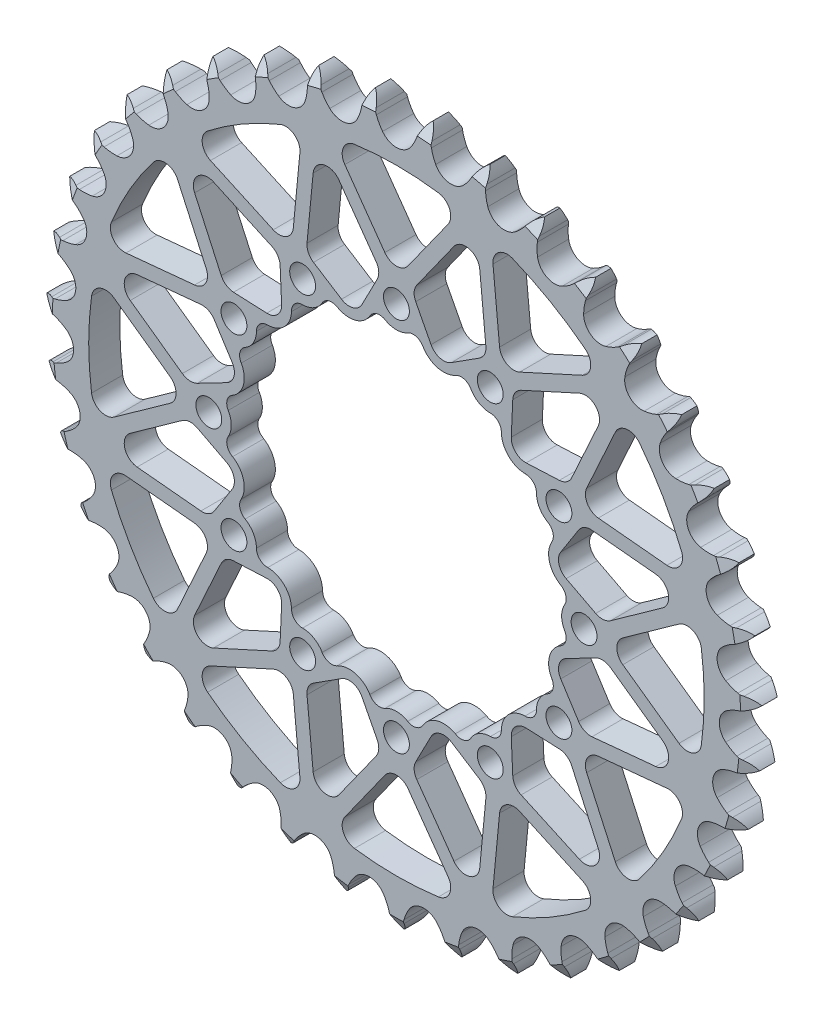
SolidWorks part; units mm, degrees
material "7075-T6 (SN)"
ref_plane "Front Plane" through (0, 0, 0) normal (0, 0, 1) x (1, 0, 0)
ref_plane "Top Plane" through (0, 0, 0) normal (0, 1, 0) x (1, 0, 0)
ref_plane "Right Plane" through (0, 0, 0) normal (1, 0, 0) x (0, 0, -1)
sketch "Work Sketch" plane through (0, 0, 0) normal (0, 0, 1) x (1, 0, 0)
  line L0 (0, 0) -> (0, 160.4542) construction
  line L1 (-112.0919, 78.9148) -> (87.2579, 78.9148) construction
  line L2 (5.102, 120.8822) -> (5.102, 112.9699) construction
  line L3 (-12.8497, 82.6953) -> (16.7256, 82.6953) construction
  line L4 (5.102, 82.6953) -> (-6.0879, 74.4036) construction
  line L5 (5.102, 82.6953) -> (-4.6505, 79.1506) construction
  line L6 (-4.6505, 79.1506) -> (-6.8863, 85.3019)
  line L7 (-11.5114, 78.0206) -> (-7.1525, 78.0206) construction
  line L8 (-11.0765, 124.7602) -> (-11.0765, 110.2345) construction
  line L9 (0, 0) -> (-3.4402, 42.6146) construction
  circle A0 centre (0, 0) radius 78.9148
  circle A1 centre (0, 78.9148) radius 4.0088
  arc A2 (-4.6505, 79.1506) -> (-3.2209, 76.5281) centre (5.0804, 82.7541) ccw
  circle A3 centre (-11.0765, 78.0206) radius 6.4254
  point P23 (-3.2209, 76.5281)
  dimension "D1" = 157.8295
  dimension "D8" = 10.3767
  dimension "D2" = 8.0177
  dimension "D3" = 5.102
  dimension "D4" = 3.7806
  dimension "D5" = 36.538
  dimension "D6" = 16.564
  dimension "D7" = 10.3767
  dimension "D9" = 0.8942
  dimension "D10" = 11.0765
  dimension "D11" = 4.615
sketch "Teeth Sketch" plane through (0, 0, 0) normal (0, 0, 1) x (1, 0, 0)
  line L0 (5.0376, 80.2155) -> (4.6505, 79.1506)
  line L1 (-7.4865, 92.7372) -> (-4.7839, 59.2593) construction
  line L2 (0, 0) -> (-10.9133, 132.3061) construction
  line L3 (7.8951, 79.9848) -> (8.1063, 78.8717)
  line L4 (16093.3137, -199351.4616) -> (-16096.7539, 199394.0762) construction
  line L5 (0, 146.3285) -> (0, 56.9858) construction
  line L6 (17.8398, 78.3686) -> (17.287, 77.3797)
  line L7 (0, -200000) -> (0, 200160.4542) construction
  line L8 (20.6234, 77.6826) -> (20.6533, 76.5499)
  line L9 (-4.6505, 79.1506) -> (-6.8863, 85.3019) construction
  line L10 (44.1616, 67.154) -> (43.8313, 66.0702)
  line L11 (-5.0376, 80.2155) -> (-4.6505, 79.1506)
  line L12 (30.18, 74.4921) -> (29.4757, 73.6046)
  line L13 (32.8175, 73.3684) -> (32.6653, 72.2456)
  line L14 (41.7385, 68.6862) -> (40.901, 67.9232)
  line L15 (52.2161, 61.1014) -> (51.267, 60.4826)
  line L16 (54.362, 59.2003) -> (53.8621, 58.1836)
  line L17 (61.3413, 51.9341) -> (60.3052, 51.4756)
  line L18 (63.1544, 49.7134) -> (62.4979, 48.79)
  line L19 (68.8777, 41.4218) -> (67.7815, 41.1354)
  line L20 (70.3112, 38.939) -> (69.515, 38.1328)
  line L21 (74.6303, 29.8366) -> (73.5023, 29.7298)
  line L22 (75.6469, 27.156) -> (74.7318, 26.488)
  line L23 (78.45, 17.4787) -> (77.3195, 17.5542)
  line L24 (79.0234, 14.6698) -> (78.013, 14.1572)
  line L25 (80.2378, 4.6681) -> (79.1341, 4.9239)
  line L26 (80.3533, 1.8035) -> (79.2737, 1.4597)
  line L27 (79.9476, -8.2634) -> (78.8992, -7.8338)
  line L28 (79.602, -11.1094) -> (78.4813, -11.2756)
  line L29 (77.5867, -20.9809) -> (76.6208, -20.3887)
  line L30 (76.7891, -23.7346) -> (75.6562, -23.7189)
  line L31 (73.2164, -33.155) -> (72.358, -32.4155)
  line L32 (71.9874, -35.7451) -> (70.8717, -35.5478)
  line L33 (66.9499, -44.4704) -> (66.2212, -43.6028)
  line L34 (65.3213, -46.8298) -> (64.2517, -46.4561)
  line L35 (58.9493, -54.634) -> (58.3693, -53.6608)
  line L36 (56.9634, -56.7016) -> (55.9676, -56.1612)
  line L37 (49.422, -63.3827) -> (49.0056, -62.329)
  line L38 (47.1301, -65.1049) -> (46.2339, -64.4118)
  line L39 (38.6147, -70.4897) -> (38.3727, -69.3829)
  line L40 (36.0763, -71.822) -> (35.3028, -70.9941)
  line L41 (26.8073, -75.7712) -> (26.746, -74.6398)
  line L42 (24.088, -76.679) -> (23.4574, -75.7377)
  line L43 (14.3056, -79.0901) -> (14.4266, -77.9636)
  line L44 (11.4759, -79.55) -> (11.0044, -78.5198)
  line L45 (1.4334, -80.3607) -> (1.7335, -79.2682)
  line L46 (-1.4334, -80.3607) -> (-1.7335, -79.2682)
  line L47 (-11.4759, -79.55) -> (-11.0044, -78.5198)
  line L48 (-14.3056, -79.0901) -> (-14.4266, -77.9636)
  line L49 (-24.088, -76.679) -> (-23.4574, -75.7377)
  line L50 (-26.8073, -75.7712) -> (-26.746, -74.6398)
  line L51 (-36.0763, -71.822) -> (-35.3028, -70.9941)
  line L52 (-38.6147, -70.4897) -> (-38.3727, -69.3829)
  line L53 (-47.1301, -65.1049) -> (-46.2339, -64.4118)
  line L54 (-49.422, -63.3827) -> (-49.0056, -62.329)
  line L55 (-56.9634, -56.7016) -> (-55.9676, -56.1612)
  line L56 (-58.9493, -54.634) -> (-58.3693, -53.6608)
  line L57 (-65.3213, -46.8298) -> (-64.2517, -46.4561)
  line L58 (-66.9499, -44.4704) -> (-66.2212, -43.6028)
  line L59 (-71.9874, -35.7451) -> (-70.8717, -35.5478)
  line L60 (-73.2164, -33.155) -> (-72.358, -32.4155)
  line L61 (-76.7891, -23.7346) -> (-75.6562, -23.7189)
  line L62 (-77.5867, -20.9809) -> (-76.6208, -20.3887)
  line L63 (-79.602, -11.1094) -> (-78.4813, -11.2756)
  line L64 (-79.9476, -8.2634) -> (-78.8992, -7.8338)
  line L65 (-80.3533, 1.8035) -> (-79.2737, 1.4597)
  line L66 (-80.2378, 4.6681) -> (-79.1341, 4.9239)
  line L67 (-79.0234, 14.6698) -> (-78.013, 14.1572)
  line L68 (-78.45, 17.4787) -> (-77.3195, 17.5542)
  line L69 (-75.6469, 27.156) -> (-74.7318, 26.488)
  line L70 (-74.6303, 29.8366) -> (-73.5023, 29.7298)
  line L71 (-70.3112, 38.939) -> (-69.515, 38.1328)
  line L72 (-68.8777, 41.4218) -> (-67.7815, 41.1354)
  line L73 (-63.1544, 49.7134) -> (-62.4979, 48.79)
  line L74 (-61.3413, 51.9341) -> (-60.3052, 51.4756)
  line L75 (-54.362, 59.2003) -> (-53.8621, 58.1836)
  line L76 (-52.2161, 61.1014) -> (-51.267, 60.4826)
  line L77 (-44.1616, 67.154) -> (-43.8313, 66.0702)
  line L78 (-41.7385, 68.6862) -> (-40.901, 67.9232)
  line L79 (-32.8175, 73.3684) -> (-32.6653, 72.2456)
  line L80 (-30.18, 74.4921) -> (-29.4757, 73.6046)
  line L81 (-20.6234, 77.6826) -> (-20.6533, 76.5499)
  line L82 (-17.8398, 78.3686) -> (-17.287, 77.3797)
  line L83 (-7.8951, 79.9848) -> (-8.1063, 78.8717)
  arc A0 (-6.8336, 82.8459) -> (-5.0376, 80.2155) centre (-11.0765, 78.0206) cw
  circle A1 centre (-11.0765, 78.0206) radius 6.4254 construction
  arc A2 (-3.2209, 76.5281) -> (-4.6505, 79.1506) centre (5.0804, 82.7541) cw
  arc A3 (-4.6505, 79.1506) -> (-3.2209, 76.5281) centre (5.0804, 82.7541) ccw construction
  circle A4 centre (0, 78.9148) radius 4.0088 construction
  arc A5 (-3.2209, 76.5281) -> (3.2209, 76.5281) centre (0, 78.9148) ccw
  arc A6 (3.2209, 76.5281) -> (4.6505, 79.1506) centre (-5.0804, 82.7541) ccw
  arc A7 (6.8336, 82.8459) -> (5.0376, 80.2155) centre (11.0765, 78.0206) ccw
  arc A8 (6.5443, 82.8692) -> (7.8951, 79.9848) centre (1.5824, 78.787) cw
  arc A9 (9.0967, 76.0537) -> (8.1063, 78.8717) centre (18.2893, 80.8676) cw
  arc A10 (9.0967, 76.0537) -> (15.4552, 75.0204) centre (12.6588, 77.8928) ccw
  arc A11 (15.4552, 75.0204) -> (17.287, 77.3797) centre (8.2601, 82.4975) ccw
  arc A12 (20.0345, 80.6769) -> (17.8398, 78.3686) centre (23.4484, 75.2334) ccw
  arc A13 (19.7528, 80.7463) -> (20.6234, 77.6826) centre (14.2002, 77.5129) cw
  arc A14 (21.1788, 73.6096) -> (20.6533, 76.5499) centre (31.0245, 76.8865) cw
  arc A15 (21.1788, 73.6096) -> (27.2892, 71.5697) centre (24.9898, 74.8535) ccw
  arc A16 (27.2892, 71.5697) -> (29.4757, 73.6046) centre (21.3867, 80.1041) ccw
  arc A17 (32.7165, 76.4184) -> (30.18, 74.4921) centre (35.2131, 70.4978) ccw
  arc A18 (32.4496, 76.5321) -> (32.8175, 73.3684) centre (26.4502, 74.2313) cw
  arc A19 (32.7124, 69.2591) -> (32.6653, 72.2456) centre (42.9562, 70.9142) cw
  arc A20 (32.7124, 69.2591) -> (38.4163, 66.2654) centre (36.6735, 69.8756) ccw
  arc A21 (38.4163, 66.2654) -> (40.901, 67.9232) centre (33.9593, 75.6361) ccw
  arc A22 (44.5512, 70.1807) -> (41.7385, 68.6862) centre (46.0657, 63.9363) ccw
  arc A23 (44.306, 70.3358) -> (44.1616, 67.154) centre (38.0153, 69.0271) cw
  arc A24 (43.3987, 63.1147) -> (43.8313, 66.0702) centre (53.7754, 63.1052) cw
  arc A25 (43.3987, 63.1147) -> (48.5486, 59.2448) centre (47.4074, 63.0878) ccw
  arc A26 (48.5486, 59.2448) -> (51.267, 60.4826) centre (45.6524, 69.2092) ccw
  arc A27 (55.2321, 62.1253) -> (52.2161, 61.1014) centre (55.7253, 55.7189) ccw
  arc A28 (55.0149, 62.3178) -> (54.362, 59.2003) centre (48.5957, 62.0351) cw
  arc A29 (52.961, 55.3358) -> (53.8621, 58.1836) centre (63.2018, 53.6618) cw
  arc A30 (52.961, 55.3358) -> (57.4234, 50.6899) centre (56.9135, 54.6662) ccw
  arc A31 (57.4234, 50.6899) -> (60.3052, 51.4756) centre (56.1632, 60.9898) ccw
  arc A32 (64.4824, 52.461) -> (61.3413, 51.9341) centre (63.9416, 46.0584) ccw
  arc A33 (64.2989, 52.6858) -> (63.1544, 49.7134) centre (57.9175, 53.4365) cw
  arc A34 (61.1517, 46.1237) -> (62.4979, 48.79) centre (70.9913, 42.8287) cw
  arc A35 (61.1517, 46.1237) -> (64.811, 40.8221) centre (64.9456, 44.8287) ccw
  arc A36 (64.811, 40.8221) -> (67.7815, 41.1354) centre (65.2193, 51.1908) ccw
  arc A37 (72.0627, 41.4379) -> (68.8777, 41.4218) centre (70.5018, 35.205) ccw
  arc A38 (71.9177, 41.6892) -> (70.3112, 38.939) centre (65.7393, 43.4539) cw
  arc A39 (67.7585, 35.717) -> (69.515, 38.1328) centre (76.9422, 30.8862) cw
  arc A40 (67.7585, 35.717) -> (70.5201, 29.8971) centre (71.2956, 33.8302) ccw
  arc A41 (70.5201, 29.8971) -> (73.5023, 29.7298) centre (72.5864, 40.0659) ccw
  arc A42 (77.7767, 29.3416) -> (74.6303, 29.8366) centre (75.2361, 23.4398) ccw
  arc A43 (77.6738, 29.6129) -> (75.6469, 27.156) centre (71.8585, 32.3458) cw
  arc A44 (72.6105, 24.3852) -> (74.7318, 26.488) centre (80.9003, 18.1439) cw
  arc A45 (72.6105, 24.3852) -> (74.4027, 18.1977) centre (75.7991, 21.9555) ccw
  arc A46 (74.4027, 18.1977) -> (77.3195, 17.5542) centre (78.0734, 27.9034) ccw
  arc A47 (81.4762, 16.4854) -> (78.45, 17.4787) centre (78.0218, 11.0675) ccw
  arc A48 (81.4182, 16.7697) -> (79.0234, 14.6698) centre (76.1166, 20.4) cw
  arc A49 (75.5818, 12.4219) -> (78.013, 14.1572) centre (82.7631, 4.9316) cw
  arc A50 (75.5818, 12.4219) -> (76.3583, 6.027) centre (78.3394, 9.5121) ccw
  arc A51 (76.3583, 6.027) -> (79.1341, 4.9239) centre (81.5384, 15.0182) ccw
  arc A52 (83.0656, 3.2022) -> (80.2378, 4.6681) centre (78.7868, -1.5914) ccw
  arc A53 (83.0539, 3.4922) -> (80.3533, 1.8035) centre (78.4033, 7.9259) cw
  arc A54 (76.5957, 0.1368) -> (79.2737, 1.4597) centre (82.4825, -8.4084) cw
  arc A55 (76.5957, 0.1368) -> (76.3363, -6.2998) centre (78.8508, -3.1776) ccw
  arc A56 (76.3363, -6.2998) -> (78.8992, -7.8338) centre (82.8916, 1.7441) ccw
  arc A57 (82.5035, -10.1639) -> (79.9476, -8.2634) centre (77.5113, -14.2091) ccw
  arc A58 (82.5385, -9.8758) -> (79.602, -11.1094) centre (78.6594, -4.7535) cw
  arc A59 (75.6257, -12.1517) -> (78.4813, -11.2756) centre (80.0655, -21.5307) cw
  arc A60 (75.6257, -12.1517) -> (74.3372, -18.4634) centre (77.3199, -15.785) ccw
  arc A61 (74.3372, -18.4634) -> (76.6208, -20.3887) centre (82.0979, -11.5753) ccw
  arc A62 (79.8047, -23.2668) -> (77.5867, -20.9809) centre (74.2283, -26.4587) ccw
  arc A63 (79.8855, -22.9881) -> (76.7891, -23.7346) centre (76.8783, -17.3098) cw
  arc A64 (72.6971, -24.1256) -> (75.6562, -23.7189) centre (75.5749, -34.0953) cw
  arc A65 (72.6971, -24.1256) -> (70.4128, -30.1488) centre (73.7866, -27.9836) ccw
  arc A66 (70.4128, -30.1488) -> (72.358, -32.4155) centre (79.178, -24.5948) ccw
  arc A67 (75.039, -35.7671) -> (73.2164, -33.155) centre (69.0227, -38.0232) ccw
  arc A68 (75.1634, -35.5049) -> (71.9874, -35.7451) centre (73.106, -29.4178) cw
  arc A69 (67.8857, -35.4746) -> (70.8717, -35.5478) centre (69.127, -45.7768) cw
  arc A70 (67.8857, -35.4746) -> (64.6648, -41.0534) centre (68.3422, -39.4574) ccw
  arc A71 (64.6648, -41.0534) -> (66.2212, -43.6028) centre (74.2074, -36.9773) ccw
  arc A72 (68.3299, -47.341) -> (66.9499, -44.4704) centre (62.0296, -48.6028) ccw
  arc A73 (68.4947, -47.1022) -> (65.3213, -46.8298) centre (67.4404, -40.7639) cw
  arc A74 (61.3161, -45.9049) -> (64.2517, -46.4561) centre (60.8887, -56.2728) cw
  arc A75 (61.3161, -45.9049) -> (57.2419, -50.8948) centre (61.1278, -49.9093) ccw
  arc A76 (57.2419, -50.8948) -> (58.3693, -53.6608) centre (67.3148, -48.4022) ccw
  arc A77 (59.851, -57.6888) -> (58.9493, -54.634) centre (53.4299, -57.9236) ccw
  arc A78 (60.052, -57.4796) -> (56.9634, -56.7016) centre (60.0281, -51.0542) cw
  arc A79 (53.1584, -55.1462) -> (55.9676, -56.1612) centre (51.0734, -65.3113) cw
  arc A80 (53.1584, -55.1462) -> (48.3366, -59.4179) centre (52.3302, -59.0685) ccw
  arc A81 (48.3366, -59.4179) -> (49.0056, -62.329) centre (58.6789, -58.5735) ccw
  arc A82 (49.822, -66.5425) -> (49.422, -63.3827) centre (43.4464, -65.7443) ccw
  arc A83 (50.054, -66.3682) -> (47.1301, -65.1049) centre (51.0611, -60.0222) cw
  arc A84 (43.6239, -62.9593) -> (46.2339, -64.4118) centre (39.9354, -72.6583) cw
  arc A85 (43.6239, -62.9593) -> (38.1793, -66.4022) centre (42.1772, -66.698) ccw
  arc A86 (38.1793, -66.4022) -> (38.3727, -69.3829) centre (48.5231, -67.2277) ccw
  arc A87 (38.5026, -73.6728) -> (38.6147, -70.4897) centre (32.3376, -71.8622) ccw
  arc A88 (38.7596, -73.538) -> (36.0763, -71.822) centre (40.7716, -67.4357) cw
  arc A89 (32.9596, -69.1417) -> (35.3028, -70.9941) centre (27.763, -78.1234) cw
  arc A90 (32.9596, -69.1417) -> (27.0333, -71.6667) centre (30.932, -72.6) ccw
  arc A91 (27.0333, -71.6667) -> (26.746, -74.6398) centre (37.1107, -74.1408) ccw
  arc A92 (26.1861, -78.8951) -> (26.8073, -75.7712) centre (20.3913, -76.1189) ccw
  arc A93 (26.4613, -78.8032) -> (24.088, -76.679) centre (29.4261, -73.1027) cw
  arc A94 (21.4417, -73.5335) -> (23.4574, -75.7377) centre (14.8716, -81.5653) cw
  arc A95 (21.4417, -73.5335) -> (15.187, -75.0751) centre (18.8855, -76.6216) ccw
  arc A96 (15.187, -75.0751) -> (14.4266, -77.9636) centre (24.7371, -79.1336) ccw
  arc A97 (13.1913, -82.0739) -> (14.3056, -79.0901) centre (7.9169, -78.4042) ccw
  arc A98 (13.4777, -82.0274) -> (11.4759, -79.55) centre (17.3186, -76.8763) cw
  arc A99 (9.3684, -76.0207) -> (11.0044, -78.5198) centre (1.595, -82.8946) cw
  arc A100 (9.3684, -76.0207) -> (2.9475, -76.5391) centre (6.35, -78.6589) ccw
  arc A101 (2.9475, -76.5391) -> (1.7335, -79.2682) centre (11.7228, -82.077) ccw
  arc A102 (-0.1451, -83.1271) -> (1.4334, -80.3607) centre (-4.7625, -78.6589) ccw
  arc A103 (0.1451, -83.1271) -> (-1.4334, -80.3607) centre (4.7625, -78.6589) cw
  arc A104 (-2.9475, -76.5391) -> (-1.7335, -79.2682) centre (-11.7228, -82.077) cw
  arc A105 (-2.9475, -76.5391) -> (-9.3684, -76.0207) centre (-6.35, -78.6589) ccw
  arc A106 (-9.3684, -76.0207) -> (-11.0044, -78.5198) centre (-1.595, -82.8946) ccw
  arc A107 (-13.4777, -82.0274) -> (-11.4759, -79.55) centre (-17.3186, -76.8763) ccw
  arc A108 (-13.1913, -82.0739) -> (-14.3056, -79.0901) centre (-7.9169, -78.4042) cw
  arc A109 (-15.187, -75.0751) -> (-14.4266, -77.9636) centre (-24.7371, -79.1336) cw
  arc A110 (-15.187, -75.0751) -> (-21.4417, -73.5335) centre (-18.8855, -76.6216) ccw
  arc A111 (-21.4417, -73.5335) -> (-23.4574, -75.7377) centre (-14.8716, -81.5653) ccw
  arc A112 (-26.4613, -78.8032) -> (-24.088, -76.679) centre (-29.4261, -73.1027) ccw
  arc A113 (-26.1861, -78.8951) -> (-26.8073, -75.7712) centre (-20.3913, -76.1189) cw
  arc A114 (-27.0333, -71.6667) -> (-26.746, -74.6398) centre (-37.1107, -74.1408) cw
  arc A115 (-27.0333, -71.6667) -> (-32.9596, -69.1417) centre (-30.932, -72.6) ccw
  arc A116 (-32.9596, -69.1417) -> (-35.3028, -70.9941) centre (-27.763, -78.1234) ccw
  arc A117 (-38.7596, -73.538) -> (-36.0763, -71.822) centre (-40.7716, -67.4357) ccw
  arc A118 (-38.5026, -73.6728) -> (-38.6147, -70.4897) centre (-32.3376, -71.8622) cw
  arc A119 (-38.1793, -66.4022) -> (-38.3727, -69.3829) centre (-48.5231, -67.2277) cw
  arc A120 (-38.1793, -66.4022) -> (-43.6239, -62.9593) centre (-42.1772, -66.698) ccw
  arc A121 (-43.6239, -62.9593) -> (-46.2339, -64.4118) centre (-39.9354, -72.6583) ccw
  arc A122 (-50.054, -66.3682) -> (-47.1301, -65.1049) centre (-51.0611, -60.0222) ccw
  arc A123 (-49.822, -66.5425) -> (-49.422, -63.3827) centre (-43.4464, -65.7443) cw
  arc A124 (-48.3366, -59.4179) -> (-49.0056, -62.329) centre (-58.6789, -58.5735) cw
  arc A125 (-48.3366, -59.4179) -> (-53.1584, -55.1462) centre (-52.3302, -59.0685) ccw
  arc A126 (-53.1584, -55.1462) -> (-55.9676, -56.1612) centre (-51.0734, -65.3113) ccw
  arc A127 (-60.052, -57.4796) -> (-56.9634, -56.7016) centre (-60.0281, -51.0542) ccw
  arc A128 (-59.851, -57.6888) -> (-58.9493, -54.634) centre (-53.4299, -57.9236) cw
  arc A129 (-57.2419, -50.8948) -> (-58.3693, -53.6608) centre (-67.3148, -48.4022) cw
  arc A130 (-57.2419, -50.8948) -> (-61.3161, -45.9049) centre (-61.1278, -49.9093) ccw
  arc A131 (-61.3161, -45.9049) -> (-64.2517, -46.4561) centre (-60.8887, -56.2728) ccw
  arc A132 (-68.4947, -47.1022) -> (-65.3213, -46.8298) centre (-67.4404, -40.7639) ccw
  arc A133 (-68.3299, -47.341) -> (-66.9499, -44.4704) centre (-62.0296, -48.6028) cw
  arc A134 (-64.6648, -41.0534) -> (-66.2212, -43.6028) centre (-74.2074, -36.9773) cw
  arc A135 (-64.6648, -41.0534) -> (-67.8857, -35.4746) centre (-68.3422, -39.4574) ccw
  arc A136 (-67.8857, -35.4746) -> (-70.8717, -35.5478) centre (-69.127, -45.7768) ccw
  arc A137 (-75.1634, -35.5049) -> (-71.9874, -35.7451) centre (-73.106, -29.4178) ccw
  arc A138 (-75.039, -35.7671) -> (-73.2164, -33.155) centre (-69.0227, -38.0232) cw
  arc A139 (-70.4128, -30.1488) -> (-72.358, -32.4155) centre (-79.178, -24.5948) cw
  arc A140 (-70.4128, -30.1488) -> (-72.6971, -24.1256) centre (-73.7866, -27.9836) ccw
  arc A141 (-72.6971, -24.1256) -> (-75.6562, -23.7189) centre (-75.5749, -34.0953) ccw
  arc A142 (-79.8855, -22.9881) -> (-76.7891, -23.7346) centre (-76.8783, -17.3098) ccw
  arc A143 (-79.8047, -23.2668) -> (-77.5867, -20.9809) centre (-74.2283, -26.4587) cw
  arc A144 (-74.3372, -18.4634) -> (-76.6208, -20.3887) centre (-82.0979, -11.5753) cw
  arc A145 (-74.3372, -18.4634) -> (-75.6257, -12.1517) centre (-77.3199, -15.785) ccw
  arc A146 (-75.6257, -12.1517) -> (-78.4813, -11.2756) centre (-80.0655, -21.5307) ccw
  arc A147 (-82.5385, -9.8758) -> (-79.602, -11.1094) centre (-78.6594, -4.7535) ccw
  arc A148 (-82.5035, -10.1639) -> (-79.9476, -8.2634) centre (-77.5113, -14.2091) cw
  arc A149 (-76.3363, -6.2998) -> (-78.8992, -7.8338) centre (-82.8916, 1.7441) cw
  arc A150 (-76.3363, -6.2998) -> (-76.5957, 0.1368) centre (-78.8508, -3.1776) ccw
  arc A151 (-76.5957, 0.1368) -> (-79.2737, 1.4597) centre (-82.4825, -8.4084) ccw
  arc A152 (-83.0539, 3.4922) -> (-80.3533, 1.8035) centre (-78.4033, 7.9259) ccw
  arc A153 (-83.0656, 3.2022) -> (-80.2378, 4.6681) centre (-78.7868, -1.5914) cw
  arc A154 (-76.3583, 6.027) -> (-79.1341, 4.9239) centre (-81.5384, 15.0182) cw
  arc A155 (-76.3583, 6.027) -> (-75.5818, 12.4219) centre (-78.3394, 9.5121) ccw
  arc A156 (-75.5818, 12.4219) -> (-78.013, 14.1572) centre (-82.7631, 4.9316) ccw
  arc A157 (-81.4182, 16.7697) -> (-79.0234, 14.6698) centre (-76.1166, 20.4) ccw
  arc A158 (-81.4762, 16.4854) -> (-78.45, 17.4787) centre (-78.0218, 11.0675) cw
  arc A159 (-74.4027, 18.1977) -> (-77.3195, 17.5542) centre (-78.0734, 27.9034) cw
  arc A160 (-74.4027, 18.1977) -> (-72.6105, 24.3852) centre (-75.7991, 21.9555) ccw
  arc A161 (-72.6105, 24.3852) -> (-74.7318, 26.488) centre (-80.9003, 18.1439) ccw
  arc A162 (-77.6738, 29.6129) -> (-75.6469, 27.156) centre (-71.8585, 32.3458) ccw
  arc A163 (-77.7767, 29.3416) -> (-74.6303, 29.8366) centre (-75.2361, 23.4398) cw
  arc A164 (-70.5201, 29.8971) -> (-73.5023, 29.7298) centre (-72.5864, 40.0659) cw
  arc A165 (-70.5201, 29.8971) -> (-67.7585, 35.717) centre (-71.2956, 33.8302) ccw
  arc A166 (-67.7585, 35.717) -> (-69.515, 38.1328) centre (-76.9422, 30.8862) ccw
  arc A167 (-71.9177, 41.6892) -> (-70.3112, 38.939) centre (-65.7393, 43.4539) ccw
  arc A168 (-72.0627, 41.4379) -> (-68.8777, 41.4218) centre (-70.5018, 35.205) cw
  arc A169 (-64.811, 40.8221) -> (-67.7815, 41.1354) centre (-65.2193, 51.1908) cw
  arc A170 (-64.811, 40.8221) -> (-61.1517, 46.1237) centre (-64.9456, 44.8287) ccw
  arc A171 (-61.1517, 46.1237) -> (-62.4979, 48.79) centre (-70.9913, 42.8287) ccw
  arc A172 (-64.2989, 52.6858) -> (-63.1544, 49.7134) centre (-57.9175, 53.4365) ccw
  arc A173 (-64.4824, 52.461) -> (-61.3413, 51.9341) centre (-63.9416, 46.0584) cw
  arc A174 (-57.4234, 50.6899) -> (-60.3052, 51.4756) centre (-56.1632, 60.9898) cw
  arc A175 (-57.4234, 50.6899) -> (-52.961, 55.3358) centre (-56.9135, 54.6662) ccw
  arc A176 (-52.961, 55.3358) -> (-53.8621, 58.1836) centre (-63.2018, 53.6618) ccw
  arc A177 (-55.0149, 62.3178) -> (-54.362, 59.2003) centre (-48.5957, 62.0351) ccw
  arc A178 (-55.2321, 62.1253) -> (-52.2161, 61.1014) centre (-55.7253, 55.7189) cw
  arc A179 (-48.5486, 59.2448) -> (-51.267, 60.4826) centre (-45.6524, 69.2092) cw
  arc A180 (-48.5486, 59.2448) -> (-43.3987, 63.1147) centre (-47.4074, 63.0878) ccw
  arc A181 (-43.3987, 63.1147) -> (-43.8313, 66.0702) centre (-53.7754, 63.1052) ccw
  arc A182 (-44.306, 70.3358) -> (-44.1616, 67.154) centre (-38.0153, 69.0271) ccw
  arc A183 (-44.5512, 70.1807) -> (-41.7385, 68.6862) centre (-46.0657, 63.9363) cw
  arc A184 (-38.4163, 66.2654) -> (-40.901, 67.9232) centre (-33.9593, 75.6361) cw
  arc A185 (-38.4163, 66.2654) -> (-32.7124, 69.2591) centre (-36.6735, 69.8756) ccw
  arc A186 (-32.7124, 69.2591) -> (-32.6653, 72.2456) centre (-42.9562, 70.9142) ccw
  arc A187 (-32.4496, 76.5321) -> (-32.8175, 73.3684) centre (-26.4502, 74.2313) ccw
  arc A188 (-32.7165, 76.4184) -> (-30.18, 74.4921) centre (-35.2131, 70.4978) cw
  arc A189 (-27.2892, 71.5697) -> (-29.4757, 73.6046) centre (-21.3867, 80.1041) cw
  arc A190 (-27.2892, 71.5697) -> (-21.1788, 73.6096) centre (-24.9898, 74.8535) ccw
  arc A191 (-21.1788, 73.6096) -> (-20.6533, 76.5499) centre (-31.0245, 76.8865) ccw
  arc A192 (-19.7528, 80.7463) -> (-20.6234, 77.6826) centre (-14.2002, 77.5129) ccw
  arc A193 (-20.0345, 80.6769) -> (-17.8398, 78.3686) centre (-23.4484, 75.2334) cw
  arc A194 (-15.4552, 75.0204) -> (-17.287, 77.3797) centre (-8.2601, 82.4975) cw
  arc A195 (-15.4552, 75.0204) -> (-9.0967, 76.0537) centre (-12.6588, 77.8928) ccw
  arc A196 (-9.0967, 76.0537) -> (-8.1063, 78.8717) centre (-18.2893, 80.8676) ccw
  arc A197 (-6.5443, 82.8692) -> (-7.8951, 79.9848) centre (-1.5824, 78.787) ccw
  point P77 (0, 0)
  dimension "D1" = 4.615
  dimension "D2" = 4.715
  dimension "D3" = 39
extrude "Extrusion" add sketch "Teeth Sketch" along normal blind 7.2136 contours A0 region at (0, 0, 0)
sketch "Sketch1" plane through (0, 0, 0) normal (0, 0, -1) x (-1, 0, 0)
  circle A0 centre (0, 0) radius 78.9443
  circle A1 centre (0, 0) radius 35.7643
  dimension "D1" = 43.18
extrude "Cut-Extrude" cut sketch "Sketch1" against normal through all both and the other way through all contours A1
ref_axis "Axis2" through (0, 0, -0.3607) along (0, 0, 1)
ref_axis "Axis1" [suppressed] through (0, 0, 7.2136) along (0, 0, -1)
ref_plane "Sprocket Center Plane" through (0, 0, 3.6068) normal (0, 0, 1) x (1, 0, 0)
sketch "Pitch Circle" plane through (0, 0, 3.6068) normal (0, 0, -1) x (-1, 0, 0)
  circle A0 centre (0, 0) radius 82.9531 construction
  dimension "D1" = 165.9063
sketch "Chain Pitch Circle" plane through (0, 0, 0) normal (0, 0, -1) x (-1, 0, 0)
  circle A0 centre (0, 0) radius 82.9531 construction
  dimension "D1" = 165.9063
ref_plane "Center Plane" through (0, 0, 3.6068) normal (0, 0, 1) x (1, 0, 0)
hole_wizard "Ø6.0mm Dowel Hole1" positions "Sketch7" profile "Sketch8" hole size "Ø6.0" standard "ANSI Metric" end condition through all
sketch "Sketch7" plane through (0, 0, 7.2136) normal (0, 0, 1) x (1, 0, 0)
  point P0 (-43.5, 0)
  dimension "D1" = 43.5
sketch "Sketch8" plane through (-43.5, 0, 7.2136) normal (1, 0, 0) x (0, -1, 0)
  line L0 (0, 0) -> (0, 7.2136)
  line L1 (0, 7.2136) -> (3, 7.2136)
  line L2 (3, 7.2136) -> (3, 0)
  line L5 (3, 0) -> (0, 0)
  line L11 (0, -6.35) -> (0, 107.95) construction
  dimension "Thru Hole Dia." = 6
  dimension "Thru Hole Depth" = 7.2136
pattern_circular "CirPattern1" count 12 over 360 about axis through (0, 0, 7.2136) along (0, 0, -1) of "Ø6.0mm Dowel Hole1" reverse direction yes
ref_plane "Plane1" through (0, 0, 3.6068) normal (0, 0, -1) x (-1, 0, 0)
sketch "Sketch9" plane through (0, 0, 0) normal (0, 0, 1) x (1, 0, 0)
  line L0 (-43.5, 0) -> (-71.3499, 0) construction
  line L1 (-69.7539, 15.0068) -> (-48.707, 0)
  line L2 (-69.7539, -15.0068) -> (-48.707, 0)
  line L11 (-43.5, 0) -> (-37.6721, 21.75) construction
  line L13 (-68.9187, 18.4667) -> (-36.1404, 9.6838) construction
  line L18 (-43.3252, 20.9264) -> (-36.1404, 9.6838)
  line L19 (-47.9839, 3.5399) -> (-36.1404, 9.6838)
  line L20 (-43.3252, 20.9264) -> (-68.9187, 18.4667)
  line L21 (-47.9839, 3.5399) -> (-68.9187, 18.4667)
  circle A0 centre (0, 0) radius 74.9059 construction
  arc A1 (-57.4234, 50.6899) -> (-52.961, 55.3358) centre (-56.9135, 54.6662) ccw construction
  circle A2 centre (-43.5, 0) radius 3 construction
  circle A3 centre (-43.5, 0) radius 5.207
  circle A4 centre (-37.6721, 21.75) radius 3 construction
  circle A6 centre (-37.6721, 21.75) radius 5.207
  circle A196 centre (0, 0) radius 71.3499
  circle A197 centre (0, 0) radius 35.7643 construction
  circle A198 centre (0, 0) radius 35.7643
  circle A199 centre (0, 0) radius 37.4153 construction
  point P17 (-40.5861, 10.875)
  dimension "D1" = 3.556
  dimension "D2" = 1.651
  dimension "D3" = 10.414
  dimension "D4" = 3.302
extrude "Cut-Extrude2" cut sketch "Sketch9" along normal through all contours L1 A196 L2 | L21 L19 L18 L20 region at (-63.4426, 0, 0) region at (-50.2379, 13.4612, 0)
fillet "Fillet2" radius 3.302 7 edges at (-68.9187, 18.4667, 3.6068) (-36.1404, 9.6838, 3.6068) (-47.9839, 3.5399, 3.6068) (-43.3252, 20.9264, 3.6068) (-69.7539, -15.0068, 3.6068) (-48.707, 0, 3.6068) (-69.7539, 15.0068, 3.6068)
pattern_circular "CirPattern3" count 12 over 360 about axis through (0, 0, 7.2136) along (0, 0, -1) of "Cut-Extrude2", "Fillet2"
sketch "Sketch14" plane through (0, 0, 7.2136) normal (0, 0, 1) x (1, 0, 0)
  line L0 (-46.191, -4.47) -> (-39.3483, -8.0197) construction
  line L1 (-38.2956, 5.9905) -> (-37.9766, 6.1559)
  line L2 (-43.5, 0) -> (-38.293, 0) construction
  line L3 (-38.2956, -5.9905) -> (-37.9766, -6.1559)
  line L4 (-30.1697, 24.3357) -> (-29.8108, 24.3195)
  line L5 (-36.1602, 13.9599) -> (-35.9667, 13.6571)
  line L6 (-13.9599, 36.1602) -> (-13.6571, 35.9667)
  line L7 (-24.3357, 30.1697) -> (-24.3195, 29.8108)
  line L8 (5.9905, 38.2956) -> (6.1559, 37.9766)
  line L9 (-5.9905, 38.2956) -> (-6.1559, 37.9766)
  line L10 (24.3357, 30.1697) -> (24.3195, 29.8108)
  line L11 (13.9599, 36.1602) -> (13.6571, 35.9667)
  line L12 (36.1602, 13.9599) -> (35.9667, 13.6571)
  line L13 (30.1697, 24.3357) -> (29.8108, 24.3195)
  line L14 (38.2956, -5.9905) -> (37.9766, -6.1559)
  line L15 (38.2956, 5.9905) -> (37.9766, 6.1559)
  line L16 (30.1697, -24.3357) -> (29.8108, -24.3195)
  line L17 (36.1602, -13.9599) -> (35.9667, -13.6571)
  line L18 (13.9599, -36.1602) -> (13.6571, -35.9667)
  line L19 (24.3357, -30.1697) -> (24.3195, -29.8108)
  line L20 (-5.9905, -38.2956) -> (-6.1559, -37.9766)
  line L21 (5.9905, -38.2956) -> (6.1559, -37.9766)
  line L22 (-24.3357, -30.1697) -> (-24.3195, -29.8108)
  line L23 (-13.9599, -36.1602) -> (-13.6571, -35.9667)
  line L24 (-36.1602, -13.9599) -> (-35.9667, -13.6571)
  line L25 (-30.1697, -24.3357) -> (-29.8108, -24.3195)
  arc A0 (-39.0014, -2.6222) -> (-39.0014, 2.6222) centre (-43.5, 0) ccw
  circle A1 centre (0, 0) radius 35.7643 construction
  arc A2 (-37.9766, -6.1559) -> (-39.0014, -2.6222) centre (-36.807, -3.9013) cw
  arc A3 (-38.2956, 5.9905) -> (-36.1602, 13.9599) centre (-40.8688, 10.9508) ccw
  arc A4 (-38.2956, 5.9905) -> (-36.1602, 13.9599) centre (-40.8688, 10.9508) ccw
  arc A5 (-37.9766, 6.1559) -> (-39.0014, 2.6222) centre (-36.807, 3.9013) ccw
  circle A6 centre (0, 0) radius 35.7643
  arc A7 (-30.1697, 24.3357) -> (-24.3357, 30.1697) centre (-29.918, 29.918) ccw
  arc A8 (-29.8108, 24.3195) -> (-32.4651, 21.7716) centre (-29.9252, 21.7821) ccw
  arc A9 (-35.0873, 17.2299) -> (-32.4651, 21.7716) centre (-37.6721, 21.75) ccw
  arc A10 (-35.9667, 13.6571) -> (-35.0873, 17.2299) centre (-33.8264, 15.0249) cw
  arc A11 (-13.9599, 36.1602) -> (-5.9905, 38.2956) centre (-10.9508, 40.8688) ccw
  arc A12 (-13.6571, 35.9667) -> (-17.2299, 35.0873) centre (-15.0249, 33.8264) ccw
  arc A13 (-21.7716, 32.4651) -> (-17.2299, 35.0873) centre (-21.75, 37.6721) ccw
  arc A14 (-24.3195, 29.8108) -> (-21.7716, 32.4651) centre (-21.7821, 29.9252) cw
  arc A15 (5.9905, 38.2956) -> (13.9599, 36.1602) centre (10.9508, 40.8688) ccw
  arc A16 (6.1559, 37.9766) -> (2.6222, 39.0014) centre (3.9013, 36.807) ccw
  arc A17 (-2.6222, 39.0014) -> (2.6222, 39.0014) centre (0, 43.5) ccw
  arc A18 (-6.1559, 37.9766) -> (-2.6222, 39.0014) centre (-3.9013, 36.807) cw
  arc A19 (24.3357, 30.1697) -> (30.1697, 24.3357) centre (29.918, 29.918) ccw
  arc A20 (24.3195, 29.8108) -> (21.7716, 32.4651) centre (21.7821, 29.9252) ccw
  arc A21 (17.2299, 35.0873) -> (21.7716, 32.4651) centre (21.75, 37.6721) ccw
  arc A22 (13.6571, 35.9667) -> (17.2299, 35.0873) centre (15.0249, 33.8264) cw
  arc A23 (36.1602, 13.9599) -> (38.2956, 5.9905) centre (40.8688, 10.9508) ccw
  arc A24 (35.9667, 13.6571) -> (35.0873, 17.2299) centre (33.8264, 15.0249) ccw
  arc A25 (32.4651, 21.7716) -> (35.0873, 17.2299) centre (37.6721, 21.75) ccw
  arc A26 (29.8108, 24.3195) -> (32.4651, 21.7716) centre (29.9252, 21.7821) cw
  arc A27 (38.2956, -5.9905) -> (36.1602, -13.9599) centre (40.8688, -10.9508) ccw
  arc A28 (37.9766, -6.1559) -> (39.0014, -2.6222) centre (36.807, -3.9013) ccw
  arc A29 (39.0014, 2.6222) -> (39.0014, -2.6222) centre (43.5, 0) ccw
  arc A30 (37.9766, 6.1559) -> (39.0014, 2.6222) centre (36.807, 3.9013) cw
  arc A31 (30.1697, -24.3357) -> (24.3357, -30.1697) centre (29.918, -29.918) ccw
  arc A32 (29.8108, -24.3195) -> (32.4651, -21.7716) centre (29.9252, -21.7821) ccw
  arc A33 (35.0873, -17.2299) -> (32.4651, -21.7716) centre (37.6721, -21.75) ccw
  arc A34 (35.9667, -13.6571) -> (35.0873, -17.2299) centre (33.8264, -15.0249) cw
  arc A35 (13.9599, -36.1602) -> (5.9905, -38.2956) centre (10.9508, -40.8688) ccw
  arc A36 (13.6571, -35.9667) -> (17.2299, -35.0873) centre (15.0249, -33.8264) ccw
  arc A37 (21.7716, -32.4651) -> (17.2299, -35.0873) centre (21.75, -37.6721) ccw
  arc A38 (24.3195, -29.8108) -> (21.7716, -32.4651) centre (21.7821, -29.9252) cw
  arc A39 (-5.9905, -38.2956) -> (-13.9599, -36.1602) centre (-10.9508, -40.8688) ccw
  arc A40 (-6.1559, -37.9766) -> (-2.6222, -39.0014) centre (-3.9013, -36.807) ccw
  arc A41 (2.6222, -39.0014) -> (-2.6222, -39.0014) centre (0, -43.5) ccw
  arc A42 (6.1559, -37.9766) -> (2.6222, -39.0014) centre (3.9013, -36.807) cw
  arc A43 (-24.3357, -30.1697) -> (-30.1697, -24.3357) centre (-29.918, -29.918) ccw
  arc A44 (-24.3195, -29.8108) -> (-21.7716, -32.4651) centre (-21.7821, -29.9252) ccw
  arc A45 (-17.2299, -35.0873) -> (-21.7716, -32.4651) centre (-21.75, -37.6721) ccw
  arc A46 (-13.6571, -35.9667) -> (-17.2299, -35.0873) centre (-15.0249, -33.8264) cw
  arc A47 (-36.1602, -13.9599) -> (-38.2956, -5.9905) centre (-40.8688, -10.9508) ccw
  arc A48 (-35.9667, -13.6571) -> (-35.0873, -17.2299) centre (-33.8264, -15.0249) ccw
  arc A49 (-32.4651, -21.7716) -> (-35.0873, -17.2299) centre (-37.6721, -21.75) ccw
  arc A50 (-29.8108, -24.3195) -> (-32.4651, -21.7716) centre (-29.9252, -21.7821) cw
  point P10 (-41.0188, -4.5778)
  point P16 (-41.0188, 4.5778)
  point P144 (0, 0)
  dimension "D2" = 2.54
  dimension "D1" = 2.286
  dimension "D3" = 12
extrude "Cut-Extrude7" cut sketch "Sketch14" against normal through all
sketch "Sketch15" plane through (0, 0, 0) normal (0, 0, -1) x (-1, 0, 0)
  line L9 (-38.264, 54.1071) -> (-28.7286, 49.7594)
  line L10 (-28.7286, 49.7594) -> (-27.7261, 60.1911)
  line L11 (-49.7594, 28.7286) -> (-54.1071, 38.264)
  line L12 (-60.1911, 27.7261) -> (-49.7594, 28.7286)
  line L13 (-49.7594, 28.7286) -> (-54.1071, 38.264)
  line L14 (-60.1911, 27.7261) -> (-49.7594, 28.7286)
  line L15 (-47.5649, 9.4801) -> (-43.4148, 11.633)
  line L16 (-54.9005, 14.7105) -> (-47.5649, 9.4801)
  line L17 (-45.9324, 15.5724) -> (-54.9005, 14.7105)
  line L18 (-43.4148, 11.633) -> (-45.9324, 15.5724)
  line L19 (-47.5649, 9.4801) -> (-43.4148, 11.633)
  line L20 (-54.9005, 14.7105) -> (-47.5649, 9.4801)
  line L21 (-45.9324, 15.5724) -> (-54.9005, 14.7105)
  line L22 (-43.4148, 11.633) -> (-45.9324, 15.5724)
  line L23 (-40.1899, 40.1899) -> (-36.4523, 31.9925)
  line L24 (-36.4523, 31.9925) -> (-31.7819, 31.7819)
  line L25 (-31.7819, 31.7819) -> (-31.9925, 36.4523)
  line L26 (-31.9925, 36.4523) -> (-40.1899, 40.1899)
  line L27 (-6.084, 65.9901) -> (0, 57.4573)
  line L28 (0, 57.4573) -> (6.084, 65.9901)
  line L29 (-14.7105, 54.9005) -> (-15.5724, 45.9324)
  line L30 (-15.5724, 45.9324) -> (-11.633, 43.4148)
  line L31 (-11.633, 43.4148) -> (-9.4801, 47.5649)
  line L32 (-9.4801, 47.5649) -> (-14.7105, 54.9005)
  line L33 (27.7261, 60.1911) -> (28.7286, 49.7594)
  line L34 (28.7286, 49.7594) -> (38.264, 54.1071)
  line L35 (14.7105, 54.9005) -> (9.4801, 47.5649)
  line L36 (9.4801, 47.5649) -> (11.633, 43.4148)
  line L37 (11.633, 43.4148) -> (15.5724, 45.9324)
  line L38 (15.5724, 45.9324) -> (14.7105, 54.9005)
  line L39 (54.1071, 38.264) -> (49.7594, 28.7286)
  line L40 (49.7594, 28.7286) -> (60.1911, 27.7261)
  line L41 (40.1899, 40.1899) -> (31.9925, 36.4523)
  line L42 (31.9925, 36.4523) -> (31.7819, 31.7819)
  line L43 (31.7819, 31.7819) -> (36.4523, 31.9925)
  line L44 (36.4523, 31.9925) -> (40.1899, 40.1899)
  line L45 (65.9901, 6.084) -> (57.4573, 0)
  line L46 (57.4573, 0) -> (65.9901, -6.084)
  line L47 (54.9005, 14.7105) -> (45.9324, 15.5724)
  line L48 (45.9324, 15.5724) -> (43.4148, 11.633)
  line L49 (43.4148, 11.633) -> (47.5649, 9.4801)
  line L50 (47.5649, 9.4801) -> (54.9005, 14.7105)
  line L51 (60.1911, -27.7261) -> (49.7594, -28.7286)
  line L52 (49.7594, -28.7286) -> (54.1071, -38.264)
  line L53 (54.9005, -14.7105) -> (47.5649, -9.4801)
  line L54 (47.5649, -9.4801) -> (43.4148, -11.633)
  line L55 (43.4148, -11.633) -> (45.9324, -15.5724)
  line L56 (45.9324, -15.5724) -> (54.9005, -14.7105)
  line L57 (38.264, -54.1071) -> (28.7286, -49.7594)
  line L58 (28.7286, -49.7594) -> (27.7261, -60.1911)
  line L59 (40.1899, -40.1899) -> (36.4523, -31.9925)
  line L60 (36.4523, -31.9925) -> (31.7819, -31.7819)
  line L61 (31.7819, -31.7819) -> (31.9925, -36.4523)
  line L62 (31.9925, -36.4523) -> (40.1899, -40.1899)
  line L63 (6.084, -65.9901) -> (0, -57.4573)
  line L64 (0, -57.4573) -> (-6.084, -65.9901)
  line L65 (14.7105, -54.9005) -> (15.5724, -45.9324)
  line L66 (15.5724, -45.9324) -> (11.633, -43.4148)
  line L67 (11.633, -43.4148) -> (9.4801, -47.5649)
  line L68 (9.4801, -47.5649) -> (14.7105, -54.9005)
  line L69 (-27.7261, -60.1911) -> (-28.7286, -49.7594)
  line L70 (-28.7286, -49.7594) -> (-38.264, -54.1071)
  line L71 (-14.7105, -54.9005) -> (-9.4801, -47.5649)
  line L72 (-9.4801, -47.5649) -> (-11.633, -43.4148)
  line L73 (-11.633, -43.4148) -> (-15.5724, -45.9324)
  line L74 (-15.5724, -45.9324) -> (-14.7105, -54.9005)
  line L75 (-54.1071, -38.264) -> (-49.7594, -28.7286)
  line L76 (-49.7594, -28.7286) -> (-60.1911, -27.7261)
  line L77 (-40.1899, -40.1899) -> (-31.9925, -36.4523)
  line L78 (-31.9925, -36.4523) -> (-31.7819, -31.7819)
  line L79 (-31.7819, -31.7819) -> (-36.4523, -31.9925)
  line L80 (-36.4523, -31.9925) -> (-40.1899, -40.1899)
  line L81 (-65.9901, -6.084) -> (-57.4573, 0)
  line L82 (-57.4573, 0) -> (-65.9901, 6.084)
  line L83 (-54.9005, -14.7105) -> (-45.9324, -15.5724)
  line L84 (-45.9324, -15.5724) -> (-43.4148, -11.633)
  line L85 (-43.4148, -11.633) -> (-47.5649, -9.4801)
  line L86 (-47.5649, -9.4801) -> (-54.9005, -14.7105)
  circle A13 centre (0, 0) radius 31.6425
  arc A18 (-27.7261, 60.1911) -> (-38.264, 54.1071) centre (0, 0) ccw
  arc A19 (6.084, 65.9901) -> (-6.084, 65.9901) centre (0, 0) ccw
  arc A20 (38.264, 54.1071) -> (27.7261, 60.1911) centre (0, 0) ccw
  arc A21 (60.1911, 27.7261) -> (54.1071, 38.264) centre (0, 0) ccw
  arc A22 (-54.1071, 38.264) -> (-60.1911, 27.7261) centre (0, 0) ccw
  arc A23 (-54.1071, 38.264) -> (-60.1911, 27.7261) centre (0, 0) ccw
  arc A24 (65.9901, -6.084) -> (65.9901, 6.084) centre (0, 0) ccw
  arc A25 (54.1071, -38.264) -> (60.1911, -27.7261) centre (0, 0) ccw
  arc A26 (27.7261, -60.1911) -> (38.264, -54.1071) centre (0, 0) ccw
  arc A27 (-6.084, -65.9901) -> (6.084, -65.9901) centre (0, 0) ccw
  arc A28 (-38.264, -54.1071) -> (-27.7261, -60.1911) centre (0, 0) ccw
  arc A29 (-60.1911, -27.7261) -> (-54.1071, -38.264) centre (0, 0) ccw
  arc A30 (-65.9901, 6.084) -> (-65.9901, -6.084) centre (0, 0) ccw
  point P3 (0, 0)
  point P28 (0, 0)
  point P123 (0, 0)
  dimension "D6" = 5.08
  dimension "D7" = 5.08
  dimension "D8" = 12
sketch "Sketch16" plane through (0, 0, 0) normal (0, 0, -1) x (-1, 0, 0)
  line L1 (88.9, 88.9) -> (-88.9, 88.9)
  line L2 (88.9, 88.9) -> (88.9, -88.9)
  line L3 (88.9, -88.9) -> (-88.9, -88.9)
  line L4 (-88.9, 88.9) -> (-88.9, -88.9)
  line L5 (88.9, 88.9) -> (-88.9, -88.9) construction
  line L6 (88.9, -88.9) -> (-88.9, 88.9) construction
  point P0 (0, 0)
  dimension "D1" = 177.8
  dimension "D2" = 177.8
sketch "Sketch17" plane through (0, 0, 0) normal (0, 0, -1) x (-1, 0, 0)
  line L0 (88.9, 88.9) -> (-88.9, -88.9) construction
  line L2 (88.9, -88.9) -> (-88.9, -88.9)
  line L3 (88.9, -88.9) -> (88.9, 88.9)
  line L4 (88.9, 88.9) -> (-88.9, 88.9)
  line L5 (-88.9, -88.9) -> (-88.9, 88.9)
  line L6 (88.9, -88.9) -> (-88.9, 88.9) construction
  line L7 (88.9, 88.9) -> (-88.9, -88.9) construction
  circle A0 centre (0, 0) radius 82.9722
sketch "Sketch21" plane through (0, 0, 7.2136) normal (0, 0, 1) x (1, 0, 0)
  arc A2 (-3.2209, 76.5281) -> (3.2209, 76.5281) centre (0, 78.9148) ccw construction
  arc A3 (6.6765, 82.7031) -> (5.0376, 80.2155) centre (11.0765, 78.0206) ccw construction
  arc A4 (3.2209, 76.5281) -> (4.6505, 79.1506) centre (-5.0804, 82.7541) ccw construction
  arc A5 (-5.0376, 80.2155) -> (-6.6765, 82.7031) centre (-11.0765, 78.0206) ccw construction
  arc A6 (-4.6505, 79.1506) -> (-3.2209, 76.5281) centre (5.0804, 82.7541) ccw construction
  spline S0 degree 3 poles (-6.6765, 82.7031) (-5.9219, 82.0275) (-5.2061, 80.8157) (-4.6311, 79.0281) (-3.5595, 76.6811) (-2.089, 74.9139) (0, 74.9059) knots 0 0 0 0 0.279448 0.385006 0.524509 1 1 1 1
  spline S1 degree 3 poles (6.6765, 82.7031) (5.9219, 82.0275) (5.2061, 80.8157) (4.6311, 79.0281) (3.5595, 76.6811) (2.089, 74.9139) (0, 74.9059) knots 0 0 0 0 0.279448 0.385006 0.524509 1 1 1 1
  spline S2 degree 3 poles (6.6765, 82.7031) (7.3129, 81.9152) (7.825, 80.6043) (8.1059, 78.7476) (8.7871, 76.2591) (9.9551, 74.2789) (12.0158, 73.9359) knots 0 0 0 0 0.279448 0.385006 0.524509 1 1 1 1
  spline S3 degree 3 poles (19.8565, 80.5611) (19.0034, 80.0153) (18.1025, 78.934) (17.2481, 77.2618) (15.814, 75.1171) (14.079, 73.6087) (12.0158, 73.9359) knots 0 0 0 0 0.279448 0.385006 0.524509 1 1 1 1
  spline S4 degree 3 poles (19.8565, 80.5611) (20.3583, 79.6813) (20.6535, 78.3052) (20.6329, 76.4275) (20.9061, 73.8621) (21.7413, 71.7201) (23.7203, 71.051) knots 0 0 0 0 0.279448 0.385006 0.524509 1 1 1 1
  spline S5 degree 3 poles (32.5223, 76.3327) (31.5926, 75.9308) (30.53, 75.008) (29.4184, 73.4945) (27.6588, 71.6077) (25.7043, 70.397) (23.7203, 71.051) knots 0 0 0 0 0.279448 0.385006 0.524509 1 1 1 1
  spline S6 degree 3 poles (32.5223, 76.3327) (32.8765, 75.3838) (32.9471, 73.9781) (32.6256, 72.1281) (32.4837, 69.552) (32.9645, 67.3038) (34.8105, 66.3259) knots 0 0 0 0 0.279448 0.385006 0.524509 1 1 1 1
  spline S7 degree 3 poles (44.3458, 70.1272) (43.3637, 69.8797) (42.1667, 69.1393) (40.8268, 67.8237) (38.7873, 66.2436) (36.664, 65.3621) (34.8105, 66.3259) knots 0 0 0 0 0.279448 0.385006 0.524509 1 1 1 1
  spline S8 degree 3 poles (44.3458, 70.1272) (44.5431, 69.1338) (44.3874, 67.7351) (43.7732, 65.9605) (43.2199, 63.4406) (43.3339, 61.1443) (44.9992, 59.883) knots 0 0 0 0 0.279448 0.385006 0.524509 1 1 1 1
  spline S9 degree 3 poles (55.0207, 62.1056) (54.0116, 62.0187) (52.7114, 61.48) (51.1778, 60.3963) (48.9113, 59.1638) (46.674, 58.6344) (44.9992, 59.883) knots 0 0 0 0 0.279448 0.385006 0.524509 1 1 1 1
  spline S10 degree 3 poles (55.0207, 62.1056) (55.0561, 61.0933) (54.678, 59.7377) (53.7872, 58.0846) (52.8368, 55.686) (52.581, 53.4013) (54.0223, 51.8892) knots 0 0 0 0 0.279448 0.385006 0.524509 1 1 1 1
  spline S11 degree 3 poles (64.2706, 52.4754) (63.2607, 52.5515) (61.8909, 52.2283) (60.2033, 51.4047) (57.7684, 50.5517) (55.4752, 50.3881) (54.0223, 51.8892) knots 0 0 0 0 0.279448 0.385006 0.524509 1 1 1 1
  spline S12 degree 3 poles (64.2706, 52.4754) (64.1432, 51.4706) (63.5526, 50.1931) (62.4081, 48.7044) (61.0853, 46.4893) (60.4662, 44.2752) (61.6464, 42.5514) knots 0 0 0 0 0.279448 0.385006 0.524509 1 1 1 1
  spline S13 degree 3 poles (71.856, 41.4861) (70.8713, 41.7233) (69.4674, 41.624) (67.6696, 41.0818) (65.1294, 40.6304) (62.8396, 40.8367) (61.6464, 42.5514) knots 0 0 0 0 0.279448 0.385006 0.524509 1 1 1 1
  spline S14 degree 3 poles (71.856, 41.4861) (71.5691, 40.5147) (70.7811, 39.3486) (69.4126, 38.0627) (67.7517, 36.0885) (66.7854, 34.0023) (67.6738, 32.1116) knots 0 0 0 0 0.279448 0.385006 0.524509 1 1 1 1
  spline S15 degree 3 poles (77.5803, 29.4223) (76.6464, 29.8144) (75.2448, 29.9416) (73.3833, 29.6948) (70.8036, 29.6568) (68.5765, 30.2277) (67.6738, 32.1116) knots 0 0 0 0 0.279448 0.385006 0.524509 1 1 1 1
  spline S16 degree 3 poles (77.5803, 29.4223) (77.1413, 28.5096) (76.1765, 27.4849) (74.6195, 26.4352) (72.6633, 24.753) (71.3749, 22.8489) (71.9485, 20.8401) knots 0 0 0 0 0.279448 0.385006 0.524509 1 1 1 1
  spline S17 degree 3 poles (81.2953, 16.5966) (80.4364, 17.1334) (79.0734, 17.4837) (77.1964, 17.5388) (74.644, 17.915) (72.5373, 18.8358) (71.9485, 20.8401) knots 0 0 0 0 0.279448 0.385006 0.524509 1 1 1 1
  spline S18 degree 3 poles (81.2953, 16.5966) (80.7156, 15.7661) (79.5989, 14.9094) (77.8937, 14.1231) (75.693, 12.7765) (74.1159, 11.1037) (74.3598, 9.0289) knots 0 0 0 0 0.279448 0.385006 0.524509 1 1 1 1
  spline S19 degree 3 poles (82.9049, 3.341) (82.1432, 4.0086) (80.854, 4.5731) (79.0101, 4.9285) (76.5511, 5.7093) (74.6195, 6.9561) (74.3598, 9.0289) knots 0 0 0 0 0.279448 0.385006 0.524509 1 1 1 1
  spline S20 degree 3 poles (82.9049, 3.341) (82.1994, 2.6142) (80.9598, 1.9478) (79.1505, 1.4452) (76.7623, 0.469) (74.9372, -0.9292) (74.8452, -3.0162) knots 0 0 0 0 0.279448 0.385006 0.524509 1 1 1 1
  spline S21 degree 3 poles (82.3672, -10.0012) (81.7225, -9.22) (80.5405, -8.456) (78.7775, -7.8095) (76.4756, -6.6443) (74.769, -5.1038) (74.8452, -3.0162) knots 0 0 0 0 0.279448 0.385006 0.524509 1 1 1 1
  spline S22 degree 3 poles (82.3672, -10.0012) (81.5543, -10.6054) (80.2238, -11.0643) (78.3573, -11.2702) (75.8435, -11.8506) (73.8178, -12.9379) (73.3921, -14.9831) knots 0 0 0 0 0.279448 0.385006 0.524509 1 1 1 1
  spline S23 degree 3 poles (79.6963, -23.0843) (79.1852, -22.2098) (78.1411, -21.2661) (76.5046, -20.3451) (74.4195, -18.8258) (72.9821, -17.0315) (73.3921, -14.9831) knots 0 0 0 0 0.279448 0.385006 0.524509 1 1 1 1
  spline S24 degree 3 poles (79.6963, -23.0843) (78.7969, -23.5502) (77.4101, -23.7898) (75.5347, -23.6936) (72.9603, -23.8633) (70.7865, -24.6116) (70.0383, -26.562) knots 0 0 0 0 0.279448 0.385006 0.524509 1 1 1 1
  spline S25 degree 3 poles (74.9612, -35.5695) (74.5971, -34.6244) (73.7178, -33.5255) (72.2503, -32.3539) (70.4359, -30.5197) (69.3049, -28.5181) (70.0383, -26.562) knots 0 0 0 0 0.279448 0.385006 0.524509 1 1 1 1
  spline S26 degree 3 poles (74.9612, -35.5695) (73.9988, -35.8852) (72.5915, -35.8992) (70.7559, -35.5034) (68.1876, -35.2579) (65.9218, -35.6478) (64.8704, -37.453) knots 0 0 0 0 0.279448 0.385006 0.524509 1 1 1 1
  spline S27 degree 3 poles (68.2847, -47.1336) (68.0769, -46.1423) (67.3854, -44.9165) (66.1248, -43.5247) (64.628, -41.4232) (63.8328, -39.2661) (64.8704, -37.453) knots 0 0 0 0 0.279448 0.385006 0.524509 1 1 1 1
  spline S28 degree 3 poles (68.2847, -47.1336) (67.2842, -47.2907) (65.8928, -47.0788) (64.1445, -46.3937) (61.6488, -45.7394) (59.3499, -45.7608) (58.0225, -47.3739) knots 0 0 0 0 0.279448 0.385006 0.524509 1 1 1 1
  spline S29 degree 3 poles (59.8397, -57.4768) (59.7936, -56.465) (59.3076, -55.1442) (58.2866, -53.5682) (57.1464, -51.2539) (56.7075, -48.9971) (58.0225, -47.3739) knots 0 0 0 0 0.279448 0.385006 0.524509 1 1 1 1
  spline S30 degree 3 poles (59.8397, -57.4768) (58.8269, -57.4715) (57.4876, -57.0391) (55.8717, -56.0824) (53.5134, -55.0362) (51.2407, -54.6886) (49.6718, -56.0679) knots 0 0 0 0 0.279448 0.385006 0.524509 1 1 1 1
  spline S31 degree 3 poles (49.8449, -66.3315) (49.9616, -65.3254) (49.6938, -63.9437) (48.9389, -62.2243) (48.1846, -59.7571) (48.1134, -57.4591) (49.6718, -56.0679) knots 0 0 0 0 0.279448 0.385006 0.524509 1 1 1 1
  spline S32 degree 3 poles (49.8449, -66.3315) (48.846, -66.1637) (47.5934, -65.5221) (46.152, -64.3186) (43.9919, -62.9077) (41.8045, -62.2) (40.0347, -63.3097) knots 0 0 0 0 0.279448 0.385006 0.524509 1 1 1 1
  spline S33 degree 3 poles (38.5591, -73.4682) (38.8357, -72.4939) (38.793, -71.0871) (38.3237, -69.2689) (37.975, -66.7126) (38.2733, -64.433) (40.0347, -63.3097) knots 0 0 0 0 0.279448 0.385006 0.524509 1 1 1 1
  spline S34 degree 3 poles (38.5591, -73.4682) (37.6001, -73.1424) (36.4666, -72.3081) (35.2369, -70.889) (33.3312, -69.1498) (31.2856, -68.1004) (29.3606, -68.9119) knots 0 0 0 0 0.279448 0.385006 0.524509 1 1 1 1
  spline S35 degree 3 poles (26.2746, -78.7021) (26.704, -77.7848) (26.8875, -76.3894) (26.7159, -74.5194) (26.7817, -71.9403) (27.4419, -69.7381) (29.3606, -68.9119) knots 0 0 0 0 0.279448 0.385006 0.524509 1 1 1 1
  spline S36 degree 3 poles (26.2746, -78.7021) (25.3803, -78.2267) (24.3953, -77.2214) (23.4092, -75.6234) (21.8071, -73.6011) (19.9564, -72.2371) (17.9262, -72.7293) knots 0 0 0 0 0.279448 0.385006 0.524509 1 1 1 1
  spline S37 degree 3 poles (13.3097, -81.8977) (13.8806, -81.0611) (14.2856, -79.7132) (14.4161, -77.84) (14.8949, -75.3048) (15.8997, -73.237) (17.9262, -72.7293) knots 0 0 0 0 0.279448 0.385006 0.524509 1 1 1 1
  spline S38 degree 3 poles (13.3097, -81.8977) (12.5032, -81.285) (11.6922, -80.1347) (10.9752, -78.3992) (9.7183, -76.1461) (8.1103, -74.5029) (6.0274, -74.663) knots 0 0 0 0 0.279448 0.385006 0.524509 1 1 1 1
  spline S39 degree 3 poles (0, -82.9722) (0.6978, -82.238) (1.3137, -80.9725) (1.7431, -79.1445) (2.6223, -76.7189) (3.9458, -74.8391) (6.0274, -74.663) knots 0 0 0 0 0.279448 0.385006 0.524509 1 1 1 1
  spline S40 degree 3 poles (0, -82.9722) (-0.6978, -82.238) (-1.3137, -80.9725) (-1.7431, -79.1445) (-2.6223, -76.7189) (-3.9458, -74.8391) (-6.0274, -74.663) knots 0 0 0 0 0.279448 0.385006 0.524509 1 1 1 1
  spline S41 degree 3 poles (-13.3097, -81.8977) (-12.5032, -81.285) (-11.6922, -80.1347) (-10.9752, -78.3992) (-9.7183, -76.1461) (-8.1103, -74.5029) (-6.0274, -74.663) knots 0 0 0 0 0.279448 0.385006 0.524509 1 1 1 1
  spline S42 degree 3 poles (-13.3097, -81.8977) (-13.8806, -81.0611) (-14.2856, -79.7132) (-14.4161, -77.84) (-14.8949, -75.3048) (-15.8997, -73.237) (-17.9262, -72.7293) knots 0 0 0 0 0.279448 0.385006 0.524509 1 1 1 1
  spline S43 degree 3 poles (-26.2746, -78.7021) (-25.3803, -78.2267) (-24.3953, -77.2214) (-23.4092, -75.6234) (-21.8071, -73.6011) (-19.9564, -72.2371) (-17.9262, -72.7293) knots 0 0 0 0 0.279448 0.385006 0.524509 1 1 1 1
  spline S44 degree 3 poles (-26.2746, -78.7021) (-26.704, -77.7848) (-26.8875, -76.3894) (-26.7159, -74.5194) (-26.7817, -71.9403) (-27.4419, -69.7381) (-29.3606, -68.9119) knots 0 0 0 0 0.279448 0.385006 0.524509 1 1 1 1
  spline S45 degree 3 poles (-38.5591, -73.4682) (-37.6001, -73.1424) (-36.4666, -72.3081) (-35.2369, -70.889) (-33.3312, -69.1498) (-31.2856, -68.1004) (-29.3606, -68.9119) knots 0 0 0 0 0.279448 0.385006 0.524509 1 1 1 1
  spline S46 degree 3 poles (-38.5591, -73.4682) (-38.8357, -72.4939) (-38.793, -71.0871) (-38.3237, -69.2689) (-37.975, -66.7126) (-38.2733, -64.433) (-40.0347, -63.3097) knots 0 0 0 0 0.279448 0.385006 0.524509 1 1 1 1
  spline S47 degree 3 poles (-49.8449, -66.3315) (-48.846, -66.1637) (-47.5934, -65.5221) (-46.152, -64.3186) (-43.9919, -62.9077) (-41.8045, -62.2) (-40.0347, -63.3097) knots 0 0 0 0 0.279448 0.385006 0.524509 1 1 1 1
  spline S48 degree 3 poles (-49.8449, -66.3315) (-49.9616, -65.3254) (-49.6938, -63.9437) (-48.9389, -62.2243) (-48.1846, -59.7571) (-48.1134, -57.4591) (-49.6718, -56.0679) knots 0 0 0 0 0.279448 0.385006 0.524509 1 1 1 1
  spline S49 degree 3 poles (-59.8397, -57.4768) (-58.8269, -57.4715) (-57.4876, -57.0391) (-55.8717, -56.0824) (-53.5134, -55.0362) (-51.2407, -54.6886) (-49.6718, -56.0679) knots 0 0 0 0 0.279448 0.385006 0.524509 1 1 1 1
  spline S50 degree 3 poles (-59.8397, -57.4768) (-59.7936, -56.465) (-59.3076, -55.1442) (-58.2866, -53.5682) (-57.1464, -51.2539) (-56.7075, -48.9971) (-58.0225, -47.3739) knots 0 0 0 0 0.279448 0.385006 0.524509 1 1 1 1
  spline S51 degree 3 poles (-68.2847, -47.1336) (-67.2842, -47.2907) (-65.8928, -47.0788) (-64.1445, -46.3937) (-61.6488, -45.7394) (-59.3499, -45.7608) (-58.0225, -47.3739) knots 0 0 0 0 0.279448 0.385006 0.524509 1 1 1 1
  spline S52 degree 3 poles (-68.2847, -47.1336) (-68.0769, -46.1423) (-67.3854, -44.9165) (-66.1248, -43.5247) (-64.628, -41.4232) (-63.8328, -39.2661) (-64.8704, -37.453) knots 0 0 0 0 0.279448 0.385006 0.524509 1 1 1 1
  spline S53 degree 3 poles (-74.9612, -35.5695) (-73.9988, -35.8852) (-72.5915, -35.8992) (-70.7559, -35.5034) (-68.1876, -35.2579) (-65.9218, -35.6478) (-64.8704, -37.453) knots 0 0 0 0 0.279448 0.385006 0.524509 1 1 1 1
  spline S54 degree 3 poles (-74.9612, -35.5695) (-74.5971, -34.6244) (-73.7178, -33.5255) (-72.2503, -32.3539) (-70.4359, -30.5197) (-69.3049, -28.5181) (-70.0383, -26.562) knots 0 0 0 0 0.279448 0.385006 0.524509 1 1 1 1
  spline S55 degree 3 poles (-79.6963, -23.0843) (-78.7969, -23.5502) (-77.4101, -23.7898) (-75.5347, -23.6936) (-72.9603, -23.8633) (-70.7865, -24.6116) (-70.0383, -26.562) knots 0 0 0 0 0.279448 0.385006 0.524509 1 1 1 1
  spline S56 degree 3 poles (-79.6963, -23.0843) (-79.1852, -22.2098) (-78.1411, -21.2661) (-76.5046, -20.3451) (-74.4195, -18.8258) (-72.9821, -17.0315) (-73.3921, -14.9831) knots 0 0 0 0 0.279448 0.385006 0.524509 1 1 1 1
  spline S57 degree 3 poles (-82.3672, -10.0012) (-81.5543, -10.6054) (-80.2238, -11.0643) (-78.3573, -11.2702) (-75.8435, -11.8506) (-73.8178, -12.9379) (-73.3921, -14.9831) knots 0 0 0 0 0.279448 0.385006 0.524509 1 1 1 1
  spline S58 degree 3 poles (-82.3672, -10.0012) (-81.7225, -9.22) (-80.5405, -8.456) (-78.7775, -7.8095) (-76.4756, -6.6443) (-74.769, -5.1038) (-74.8452, -3.0162) knots 0 0 0 0 0.279448 0.385006 0.524509 1 1 1 1
  spline S59 degree 3 poles (-82.9049, 3.341) (-82.1994, 2.6142) (-80.9598, 1.9478) (-79.1505, 1.4452) (-76.7623, 0.469) (-74.9372, -0.9292) (-74.8452, -3.0162) knots 0 0 0 0 0.279448 0.385006 0.524509 1 1 1 1
  spline S60 degree 3 poles (-82.9049, 3.341) (-82.1432, 4.0086) (-80.854, 4.5731) (-79.0101, 4.9285) (-76.5511, 5.7093) (-74.6195, 6.9561) (-74.3598, 9.0289) knots 0 0 0 0 0.279448 0.385006 0.524509 1 1 1 1
  spline S61 degree 3 poles (-81.2953, 16.5966) (-80.7156, 15.7661) (-79.5989, 14.9094) (-77.8937, 14.1231) (-75.693, 12.7765) (-74.1159, 11.1037) (-74.3598, 9.0289) knots 0 0 0 0 0.279448 0.385006 0.524509 1 1 1 1
  spline S62 degree 3 poles (-81.2953, 16.5966) (-80.4364, 17.1334) (-79.0734, 17.4837) (-77.1964, 17.5388) (-74.644, 17.915) (-72.5373, 18.8358) (-71.9485, 20.8401) knots 0 0 0 0 0.279448 0.385006 0.524509 1 1 1 1
  spline S63 degree 3 poles (-77.5803, 29.4223) (-77.1413, 28.5096) (-76.1765, 27.4849) (-74.6195, 26.4352) (-72.6633, 24.753) (-71.3749, 22.8489) (-71.9485, 20.8401) knots 0 0 0 0 0.279448 0.385006 0.524509 1 1 1 1
  spline S64 degree 3 poles (-77.5803, 29.4223) (-76.6464, 29.8144) (-75.2448, 29.9416) (-73.3833, 29.6948) (-70.8036, 29.6568) (-68.5765, 30.2277) (-67.6738, 32.1116) knots 0 0 0 0 0.279448 0.385006 0.524509 1 1 1 1
  spline S65 degree 3 poles (-71.856, 41.4861) (-71.5691, 40.5147) (-70.7811, 39.3486) (-69.4126, 38.0627) (-67.7517, 36.0885) (-66.7854, 34.0023) (-67.6738, 32.1116) knots 0 0 0 0 0.279448 0.385006 0.524509 1 1 1 1
  spline S66 degree 3 poles (-71.856, 41.4861) (-70.8713, 41.7233) (-69.4674, 41.624) (-67.6696, 41.0818) (-65.1294, 40.6304) (-62.8396, 40.8367) (-61.6464, 42.5514) knots 0 0 0 0 0.279448 0.385006 0.524509 1 1 1 1
  spline S67 degree 3 poles (-64.2706, 52.4754) (-64.1432, 51.4706) (-63.5526, 50.1931) (-62.4081, 48.7044) (-61.0853, 46.4893) (-60.4662, 44.2752) (-61.6464, 42.5514) knots 0 0 0 0 0.279448 0.385006 0.524509 1 1 1 1
  spline S68 degree 3 poles (-64.2706, 52.4754) (-63.2607, 52.5515) (-61.8909, 52.2283) (-60.2033, 51.4047) (-57.7684, 50.5517) (-55.4752, 50.3881) (-54.0223, 51.8892) knots 0 0 0 0 0.279448 0.385006 0.524509 1 1 1 1
  spline S69 degree 3 poles (-55.0207, 62.1056) (-55.0561, 61.0933) (-54.678, 59.7377) (-53.7872, 58.0846) (-52.8368, 55.686) (-52.581, 53.4013) (-54.0223, 51.8892) knots 0 0 0 0 0.279448 0.385006 0.524509 1 1 1 1
  spline S70 degree 3 poles (-55.0207, 62.1056) (-54.0116, 62.0187) (-52.7114, 61.48) (-51.1778, 60.3963) (-48.9113, 59.1638) (-46.674, 58.6344) (-44.9992, 59.883) knots 0 0 0 0 0.279448 0.385006 0.524509 1 1 1 1
  spline S71 degree 3 poles (-44.3458, 70.1272) (-44.5431, 69.1338) (-44.3874, 67.7351) (-43.7732, 65.9605) (-43.2199, 63.4406) (-43.3339, 61.1443) (-44.9992, 59.883) knots 0 0 0 0 0.279448 0.385006 0.524509 1 1 1 1
  spline S72 degree 3 poles (-44.3458, 70.1272) (-43.3637, 69.8797) (-42.1667, 69.1393) (-40.8268, 67.8237) (-38.7873, 66.2436) (-36.664, 65.3621) (-34.8105, 66.3259) knots 0 0 0 0 0.279448 0.385006 0.524509 1 1 1 1
  spline S73 degree 3 poles (-32.5223, 76.3327) (-32.8765, 75.3838) (-32.9471, 73.9781) (-32.6256, 72.1281) (-32.4837, 69.552) (-32.9645, 67.3038) (-34.8105, 66.3259) knots 0 0 0 0 0.279448 0.385006 0.524509 1 1 1 1
  spline S74 degree 3 poles (-32.5223, 76.3327) (-31.5926, 75.9308) (-30.53, 75.008) (-29.4184, 73.4945) (-27.6588, 71.6077) (-25.7043, 70.397) (-23.7203, 71.051) knots 0 0 0 0 0.279448 0.385006 0.524509 1 1 1 1
  spline S75 degree 3 poles (-19.8565, 80.5611) (-20.3583, 79.6813) (-20.6535, 78.3052) (-20.6329, 76.4275) (-20.9061, 73.8621) (-21.7413, 71.7201) (-23.7203, 71.051) knots 0 0 0 0 0.279448 0.385006 0.524509 1 1 1 1
  spline S76 degree 3 poles (-19.8565, 80.5611) (-19.0034, 80.0153) (-18.1025, 78.934) (-17.2481, 77.2618) (-15.814, 75.1171) (-14.079, 73.6087) (-12.0158, 73.9359) knots 0 0 0 0 0.279448 0.385006 0.524509 1 1 1 1
  spline S77 degree 3 poles (-6.6765, 82.7031) (-7.3129, 81.9152) (-7.825, 80.6043) (-8.1059, 78.7476) (-8.7871, 76.2591) (-9.9551, 74.2789) (-12.0158, 73.9359) knots 0 0 0 0 0.279448 0.385006 0.524509 1 1 1 1
  point P534 (0, 0)
sketch "Sketch18" plane through (0, 0, 0) normal (1, 0, 0) x (0, 0, -1)
  line L0 (-1.8288, -82.9722) -> (-5.3848, -82.9722)
  line L1 (-5.3848, -82.9722) -> (-5.3848, -79.7786)
  line L2 (-5.3848, -79.7786) -> (-7.2136, -79.7786)
  line L3 (-7.2136, -79.7786) -> (-5.3848, -82.9722)
  line L4 (-7.2136, -79.7786) -> (-7.2136, -82.9722)
  line L5 (-7.2136, -82.9722) -> (-5.3848, -82.9722)
  line L6 (-7.2136, -79.7786) -> (-7.2136, -82.9722)
  line L7 (-5.3848, -82.9722) -> (-7.2136, -79.7786)
  dimension "D1" = 3.556
  dimension "D2" = 3.1936
  dimension "D3" = 1.8288
revolve "Cut-Revolve2" cut sketch "Sketch18" angle 360 about axis through (0, 0, -0.3607) along (0, 0, 1) region at (0, -81.9076, 6.604)
mirror "Mirror1" about plane through (0, 0, 3.6068) normal (0, 0, -1) of "Cut-Revolve2"
equation "\"P\"= 0.500'//Chain Pitch"
equation "\"N\"= 39'//Number of Teeth"
equation "\"Dr\"= 5 / 16'//Roller Diameter"
equation "\"Ds\"= 1.0005 * \"Dr\" + 0.003'Seating Curve DIameter"
equation "\"R\"= \"Ds\" / 2"
equation "\"A\"= 35 + 60 / \"N\""
equation "\"B\"= 18 - 56 / \"N\""
equation "\"ac\"= 0.8 * \"Dr\""
equation "\"M\"= 0.8 * \"Dr\" * cos ( 35 + 60 / \"N\" )"
equation "\"T\"= 0.8 * \"Dr\" * sin ( 35 + 60 / \"N\" )"
equation "\"E\"= 1.3025 * \"Dr\" + 0.0015"
equation "\"Chordal Length of Arc xy\"= ( 2.605 * \"Dr\" + 0.003 ) * sin ( 9 - 28 / \"N\" )"
equation "\"yz\"= \"Dr\" * ( 1.4 * sin ( 17 - 64 / \"N\" ) - 0.8 * sin ( 18 - 56 / \"N\" ) )"
equation "\"ab\"= 1.4 * \"Dr\""
equation "\"W\"= 1.4 * \"Dr\" * cos ( 180 / \"N\" )"
equation "\"V\"= 1.4 * \"Dr\" * sin ( 180 / \"N\" )"
equation "\"F\"= \"Dr\" * ( 0.8 * cos ( 18 - 56 / \"N\" ) + 1.4 * cos ( 17 - 64 / \"N\" ) - 1.3025 )"
equation "\"H\"= sqr ( \"F\" ^ 2 - ( 1.4 * \"Dr\" - \"P\" / 2 ) ^ 2 )"
equation "\"S\"= \"P\" / 2 * cos ( 180 / \"N\" ) + \"H\" * sin ( 180 / \"N\" )"
equation "\"PD\"= \"P\" / ( sin ( 180 / \"N\" ) )"
equation "\"D1@Work Sketch\" = \"PD\""
equation "\"D3@Work Sketch\" = \"M\""
equation "\"D4@Work Sketch\" = \"T\""
equation "\"D5@Work Sketch\" = \"A\""
equation "\"D6@Work Sketch\" = \"B\""
equation "\"D7@Work Sketch\" = \"E\""
equation "\"D8@Work Sketch\" = \"E\""
equation "\"D9@Work Sketch\" = \"V\""
equation "\"D10@Work Sketch\" = \"W\""
equation "\"D2@Work Sketch\" = \"R\" * 2"
equation "\"D11@Work Sketch\" = 180 / \"N\""
equation "\"D2@Teeth Sketch\" = 180 / \"N\" + 0.1"
equation "\"D3@Teeth Sketch\" = \"N\""
equation "\"Edge Thickness\"=1.7"
equation "\"D1@Sketch1\"=\"Edge Thickness\""
equation "\"InnerRib\"=0.060000"
equation "\"ST\"= 0.284'//Sprocket Thickness"
